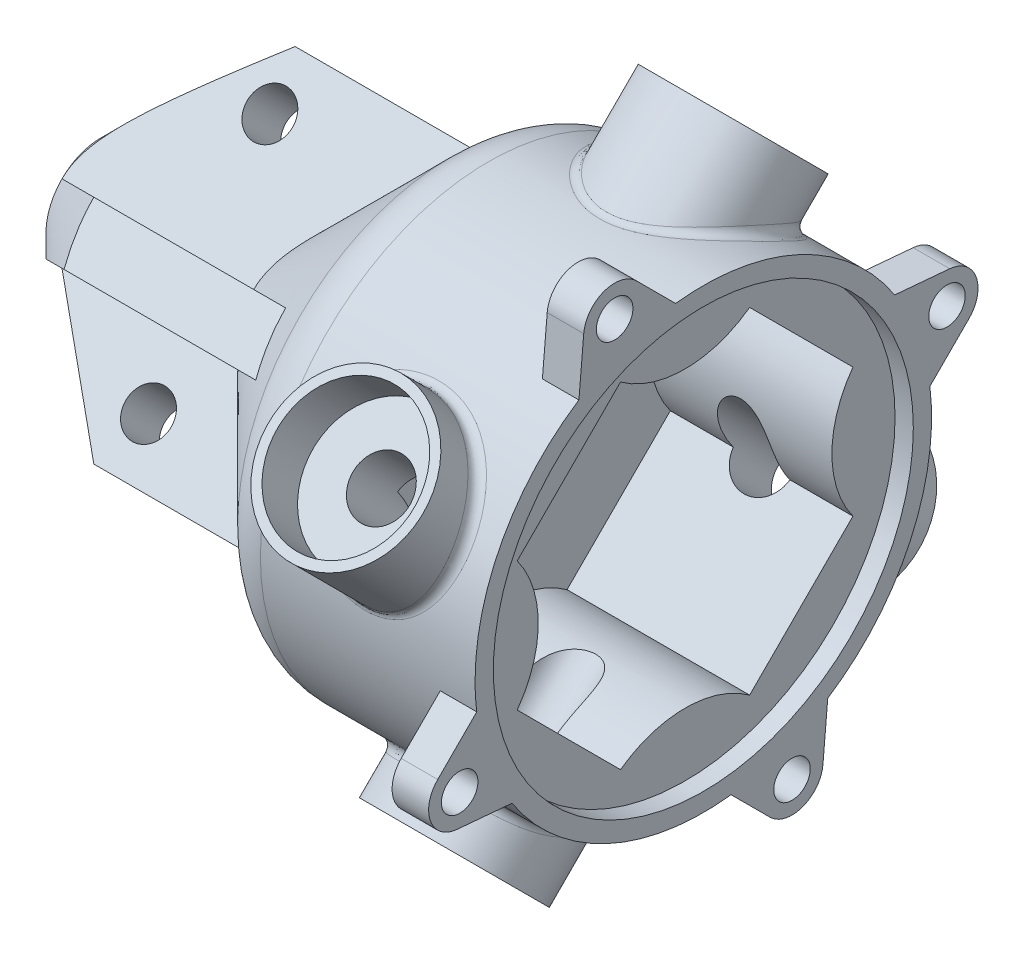
SolidWorks part; units mm, degrees
ref_plane "Front Plane" through (0, 0, 0) normal (0, 0, 1) x (1, 0, 0)
ref_plane "Top Plane" through (0, 0, 0) normal (0, 1, 0) x (1, 0, 0)
ref_plane "Right Plane" through (0, 0, 0) normal (1, 0, 0) x (0, 0, -1)
sketch "Sketch2" plane through (0, 0, 0) normal (1, 0, 0) x (0, 0, -1)
  circle A0 centre (0, 0) radius 31.75
  dimension "D1" = 63.5
extrude "Boss-Extrude1" add sketch "Sketch2" along normal blind 27.94 contours A0
ref_axis "Axis1" through (-1.27, 0, 0) along (1, 0, 0)
ref_plane "Plane1" through (0, 0, 0) normal (0, -0.7071, 0.7071) x (1, 0, 0)
sketch "Sketch3" plane through (0, 0, 0) normal (0, 0.7071, -0.7071) x (1, 0, 0)
  circle A0 centre (12.7, 10.668) radius 10.795
  dimension "D3" = 21.59
  dimension "D1" = 10.668
  dimension "D2" = 12.7
extrude "Boss-Extrude2" add sketch "Sketch3" against normal blind 38.1
sketch "Sketch4" plane through (0, -26.9408, 26.9408) normal (0, -0.7071, 0.7071) x (-1, 0, 0)
  circle A0 centre (-12.7, 10.668) radius 3.9688
  circle A1 centre (-12.7, 10.668) radius 10.795 construction
  dimension "D1" = 7.9375
extrude "Cut-Extrude1" cut sketch "Sketch4" against normal blind 25.4
sketch "Sketch9" plane through (0, -26.9408, 26.9408) normal (0, -0.7071, 0.7071) x (-1, 0, 0)
  circle A0 centre (-12.7, 10.668) radius 9.525
  circle A1 centre (-12.7, 10.668) radius 3.9688 construction
  dimension "D1" = 19.05
extrude "Cut-Extrude6" cut sketch "Sketch9" against normal blind 6.985
pattern_circular "CirPattern14" count 4 over 360 about axis through (0, 0, 0) along (1, 0, 0) of "Cut-Extrude1", "Boss-Extrude2", "Cut-Extrude6"
sketch "Sketch10" plane through (0, 0, 0) normal (1, 0, 0) x (0, 0, -1)
  line L1 (-5.969, 16.616) -> (5.969, 16.616)
  line L2 (-5.969, 16.616) -> (-5.969, 8.616)
  line L3 (-5.969, 8.616) -> (5.969, 8.616)
  line L4 (5.969, 16.616) -> (5.969, 8.616)
  line L5 (-5.969, 16.616) -> (5.969, 8.616) construction
  line L6 (-5.969, 8.616) -> (5.969, 16.616) construction
  line L7 (16.616, 5.969) -> (16.616, -5.969)
  line L8 (16.616, 5.969) -> (8.616, 5.969)
  line L9 (8.616, 5.969) -> (8.616, -5.969)
  line L10 (16.616, -5.969) -> (8.616, -5.969)
  line L11 (16.616, 5.969) -> (8.616, -5.969) construction
  line L12 (8.616, 5.969) -> (16.616, -5.969) construction
  line L13 (5.969, -16.616) -> (-5.969, -16.616)
  line L14 (5.969, -16.616) -> (5.969, -8.616)
  line L15 (5.969, -8.616) -> (-5.969, -8.616)
  line L16 (-5.969, -16.616) -> (-5.969, -8.616)
  line L17 (5.969, -16.616) -> (-5.969, -8.616) construction
  line L18 (5.969, -8.616) -> (-5.969, -16.616) construction
  line L19 (-16.616, -5.969) -> (-16.616, 5.969)
  line L20 (-16.616, -5.969) -> (-8.616, -5.969)
  line L21 (-8.616, -5.969) -> (-8.616, 5.969)
  line L22 (-16.616, 5.969) -> (-8.616, 5.969)
  line L23 (-16.616, -5.969) -> (-8.616, 5.969) construction
  line L24 (-8.616, -5.969) -> (-16.616, 5.969) construction
  point P0 (0, 12.616)
  point P6 (12.616, 0)
  point P16 (0, -12.616)
  point P21 (-12.616, 0)
  dimension "D1" = 11.938
  dimension "D2" = 8
  dimension "D3" = 4
sketch "Sketch5" plane through (0, 0, 0) normal (1, 0, 0) x (0, 0, -1)
  line L0 (0, 0) -> (0, 50000) construction
  line L1 (0, 0) -> (50000, 0) construction
  line L14 (0, 22.86) -> (10.16, 22.86)
  line L15 (22.86, 0) -> (22.86, -10.16)
  line L16 (10.16, -22.86) -> (0, -22.86)
  line L17 (22.86, 10.16) -> (22.86, 0)
  line L18 (0, -22.86) -> (-10.16, -22.86)
  line L19 (-22.86, -10.16) -> (-22.86, 0)
  line L20 (-22.86, 0) -> (-22.86, 10.16)
  line L21 (-10.16, 22.86) -> (0, 22.86)
  arc A2 (10.16, 22.86) -> (22.86, 10.16) centre (25.2167, 25.2167) ccw
  arc A4 (22.86, -10.16) -> (10.16, -22.86) centre (25.2167, -25.2167) ccw
  arc A5 (-10.16, -22.86) -> (-22.86, -10.16) centre (-25.2167, -25.2167) ccw
  arc A6 (-22.86, 10.16) -> (-10.16, 22.86) centre (-25.2167, 25.2167) ccw
  dimension "D1" = 10.16
  dimension "D4" = 15.24
  dimension "D2" = 10.16
  dimension "D3" = 22.86
  dimension "D5" = 22.86
  dimension "D6" = 4
extrude "Cut-Extrude3" [suppressed] cut sketch "Sketch5" along normal through all
sketch "Sketch11" plane through (0, 0, 0) normal (1, 0, 0) x (0, 0, -1)
  line L0 (-0.0688, -0.0688) -> (6.9431, 6.9431) construction
  line L1 (-0.9455, 0.9455) -> (5.706, -5.706) construction
  line L2 (22.5403, 22.3607) -> (27.0306, 26.851) construction
  line L3 (-23.3487, 8.9803) -> (-8.9803, 23.3487)
  line L4 (23.3487, 8.9803) -> (8.9803, 23.3487)
  line L5 (8.9803, -23.3487) -> (23.3487, -8.9803)
  line L6 (-8.9803, -23.3487) -> (-23.3487, -8.9803)
  arc A0 (-8.9803, 23.3487) -> (8.9803, 23.3487) centre (0, 35.6618) ccw
  arc A1 (23.3487, -8.9803) -> (23.3487, 8.9803) centre (35.6618, 0) cw
  arc A2 (8.9803, -23.3487) -> (-8.9803, -23.3487) centre (0, -35.6618) ccw
  arc A3 (-23.3487, 8.9803) -> (-23.3487, -8.9803) centre (-35.6618, 0) cw
  point P12 (16.1645, 16.1645)
  point P17 (16.1645, -16.1645)
  point P22 (-16.1645, 16.1645)
  dimension "D1" = 15.24
  dimension "D2" = 10.16
  dimension "D3" = 10.16
  dimension "D4" = 22.86
  dimension "D5" = 22.86
extrude "Cut-Extrude7" cut sketch "Sketch11" along normal through all
sketch "Sketch6" plane through (0, 0, 0) normal (0, 0, 1) x (1, 0, 0)
  line L0 (0, 0) -> (-50000, 0) construction
  line L1 (0, 31.75) -> (0, -31.75) construction
  line L2 (-5.08, 0) -> (-5.08, 2.5)
  line L3 (-5.08, 2.5) -> (0, 2.5)
  line L4 (0, 2.5) -> (0, 31.75)
  line L5 (0, 31.75) -> (-5.08, 31.75)
  line L6 (-5.08, 31.75) -> (-36.83, 0)
  line L11 (-36.83, 0) -> (-5.08, 0)
  line L12 (27.94, 31.75) -> (0, 31.75) construction
  point P4 (0, 0)
  dimension "D1" = 5
  dimension "D2" = 5.08
  dimension "D4" = 45
revolve "Revolve1" add sketch "Sketch6" angle 360 about L0
sketch "Sketch7" plane through (0, 0, 0) normal (0, -0.7071, 0.7071) x (1, 0, 0)
  line L0 (12.7, -10.668) -> (-49987.3, -10.668) construction
  circle A0 centre (-38.1, -15.748) radius 3.175 construction
  circle A1 centre (12.7, -10.668) radius 3.9688 construction
  circle A2 centre (-38.1, -15.748) radius 6.985
  dimension "D1" = 6.35
  dimension "D2" = 13.97
  dimension "D4" = 50.8
  dimension "D3" = 5.08
extrude "Boss-Extrude3" add sketch "Sketch7" against normal blind 7.62
sketch "Sketch19" plane through (-5.08, -3.5921, 3.5921) normal (-1, 0, 0) x (0, -0.7071, 0.7071)
  line L8 (-5.08, 0) -> (-5.08, -22.733)
  line L9 (-5.08, -22.733) -> (-12.7, -22.733)
  line L10 (-12.7, -22.733) -> (-12.7, 0)
  line L11 (-12.7, 0) -> (-5.08, 0)
extrude "Boss-Extrude8" add sketch "Sketch19" along normal blind 50.8
pattern_circular "CirPattern19" count 4 over 360 about axis through (27.94, 0, 0) along (-1, 0, 0) of "Boss-Extrude8" reverse direction yes
sketch "Sketch20" plane through (0, 0, 0) normal (0, -0.7071, 0.7071) x (1, 0, 0)
  line L3 (-31.75, -31.75) -> (-55.88, -7.62)
  line L4 (-14.097, -22.733) -> (-5.08, -31.75) construction
  line L5 (0, 0) -> (-50000, 0) construction
  line L6 (-55.88, -7.62) -> (-55.88, -31.75)
  line L7 (-55.88, -31.75) -> (-31.75, -31.75)
  line L8 (-55.88, -22.733) -> (-55.88, -7.62) construction
  line L9 (-5.08, -31.75) -> (11.049, -31.75) construction
sketch "Sketch8" plane through (0, 0, 0) normal (0, 0.7071, -0.7071) x (1, 0, 0)
  circle A0 centre (-38.1, 15.748) radius 3.175
  circle A1 centre (-38.1, 15.748) radius 3.175 construction
extrude "Cut-Extrude4" cut sketch "Sketch8" along normal through all
pattern_circular "CirPattern16" count 4 over 360 about axis through (-5.08, 0, 0) along (-1, 0, 0) of "Cut-Extrude4"
revolve "Cut-Revolve1" cut sketch "Sketch20" angle 360 about L5
fillet "Fillet4" radius 7.62 1 edges at (-5.08, 0, -31.75)
fillet "Fillet5" radius 1.27 4 edges at (11.5999, 1.4434, 31.7172) (11.5999, -31.7172, 1.4434) (11.5999, 31.7172, -1.4434) (11.5999, -1.4434, -31.7172)
sketch "Sketch16" plane through (0, 0, 0) normal (1, 0, 0) x (0, 0, -1)
  line L0 (0, 0) -> (-17068.6726, 46895.7925) construction
  line L2 (0, 43.307) -> (0, -43.307) construction
  dimension "D1" = 20
sketch "Sketch14" plane through (27.94, 0, 0) normal (1, 0, 0) x (0, 0, -1)
  line L6 (-17.3069, 26.6183) -> (-16.6376, 34.2692)
  line L8 (-3.852, 31.5155) -> (-9.2827, 36.9461)
  line L9 (68404.0287, -187938.5242) -> (-85472.7012, 234834.3166) construction
  line L10 (-13.8128, 37.9504) -> (-13.2047, 36.2797) construction
  line L11 (-11.4673, 31.506) -> (-10.8591, 29.8352) construction
  arc A8 (-17.3069, 26.6183) -> (-3.852, 31.5155) centre (0, 0) cw
  circle A9 centre (0, 0) radius 31.75 construction
  arc A10 (-16.6376, 34.2692) -> (-9.2827, 36.9461) centre (-12.336, 33.8928) cw
  circle A11 centre (-12.336, 33.8928) radius 2.54
  dimension "D2" = 4.318
  dimension "D3" = 25
  dimension "D1" = 5.08
  dimension "D4" = 25
extrude "Boss-Extrude4" add sketch "Sketch14" against normal blind 5.08
pattern_circular "CirPattern15" count 4 over 360 about axis through (27.94, 0, 0) along (-1, 0, 0) of "Boss-Extrude4"
sketch "Sketch15" plane through (27.94, 0, 0) normal (1, 0, 0) x (0, 0, -1)
  circle A0 centre (0, 0) radius 29.21
  arc A2 (26.6183, 17.3069) -> (-3.852, 31.5155) centre (0, 0) ccw construction
  dimension "D1" = 2.54
extrude "Cut-Extrude8" cut sketch "Sketch15" against normal blind 2.54
